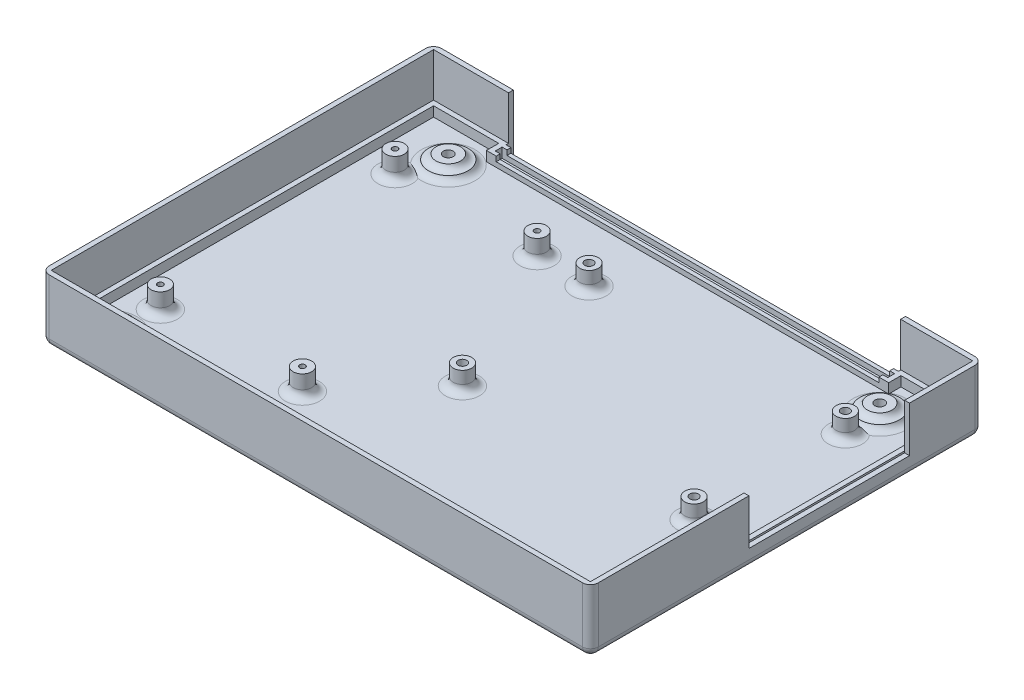
SolidWorks part; units mm, degrees
ref_plane "Front Plane" through (0, 0, 0) normal (0, 0, 1) x (1, 0, 0)
ref_plane "Top Plane" through (0, 0, 0) normal (0, 1, 0) x (1, 0, 0)
ref_plane "Right Plane" through (0, 0, 0) normal (1, 0, 0) x (0, 0, -1)
sketch "Sketch1" plane through (0, 0, 0) normal (0, 1, 0) x (1, 0, 0)
  line L1 (-88.9, -63.5) -> (88.9, -63.5)
  line L2 (-88.9, -63.5) -> (-88.9, 63.5)
  line L3 (-88.9, 63.5) -> (88.9, 63.5)
  line L4 (88.9, -63.5) -> (88.9, 63.5)
  line L5 (-88.9, -63.5) -> (88.9, 63.5) construction
  line L6 (-88.9, 63.5) -> (88.9, -63.5) construction
  point P0 (0, 0)
  dimension "D1" = 177.8
  dimension "D2" = 127
extrude "Boss-Extrude1" add sketch "Sketch1" along normal blind 20.525
sketch "Sketch2" plane through (0, 20.525, 0) normal (0, 1, 0) x (1, 0, 0)
  line L1 (-87.3125, -61.9125) -> (87.3125, -61.9125)
  line L2 (-87.3125, -61.9125) -> (-87.3125, 61.9125)
  line L3 (-87.3125, 61.9125) -> (87.3125, 61.9125)
  line L4 (87.3125, -61.9125) -> (87.3125, 61.9125)
  line L5 (-87.3125, -61.9125) -> (87.3125, 61.9125) construction
  line L6 (-87.3125, 61.9125) -> (87.3125, -61.9125) construction
  point P0 (0, 0)
  dimension "D1" = 174.625
  dimension "D2" = 123.825
extrude "Cut-Extrude1" cut sketch "Sketch2" against normal blind 14.175
fillet "Fillet2" radius 2.54 8 edges at (-88.9, 10.2625, -63.5) (0, 0, -63.5) (88.9, 10.2625, -63.5) (88.9, 0, 0) (88.9, 10.2625, 63.5) (-88.9, 10.2625, 63.5) (-88.9, 0, 0) (0, 0, 63.5)
sketch "Sketch4" plane through (0, 6.35, 0) normal (0, 1, 0) x (1, 0, 0)
  line L0 (87.3125, 61.9125) -> (-87.3125, 61.9125) construction
  line L1 (-63.05, 61.9125) -> (63.95, 61.9125)
  line L2 (-63.05, 61.9125) -> (-63.05, 63.5)
  line L3 (-63.05, 63.5) -> (63.95, 63.5)
  line L4 (63.95, 61.9125) -> (63.95, 63.5)
  line L5 (86.36, 63.5) -> (-86.36, 63.5) construction
  point P8 (0.45, 61.9125)
  dimension "D1" = 63.5
  dimension "D2" = 63.5
  dimension "D3" = 127
extrude "Cut-Extrude2" cut sketch "Sketch4" along normal blind 17.175
sketch "Sketch11" plane through (0, 0, 0) normal (0, 1, 0) x (1, 0, 0)
  line L1 (-85.725, -60.325) -> (85.725, -60.325)
  line L2 (-85.725, -60.325) -> (-85.725, 60.325)
  line L3 (-85.725, 60.325) -> (85.725, 60.325)
  line L4 (85.725, -60.325) -> (85.725, 60.325)
  line L5 (-85.725, -60.325) -> (85.725, 60.325) construction
  line L6 (-85.725, 60.325) -> (85.725, -60.325) construction
  point P0 (0, 0)
  dimension "D1" = 171.45
  dimension "D2" = 120.65
extrude "Cut-Extrude3" cut sketch "Sketch11" along normal blind 3.175 from offset 3.175
sketch "Sketch7" plane through (0, 0, 0) normal (0, 1, 0) x (1, 0, 0)
  line L0 (-87.3125, -61.9125) -> (87.3125, -61.9125) construction
  line L1 (-51.6011, -60.325) -> (-33.4411, -60.325)
  line L2 (-51.6011, -60.325) -> (-51.6011, -58.1104)
  line L3 (-51.6011, -58.1104) -> (-33.4411, -58.1104)
  line L4 (-33.4411, -60.325) -> (-33.4411, -58.1104)
  point P4 (-42.5211, -60.325)
  dimension "D1" = 1.5875
extrude "Boss-Extrude3" add sketch "Sketch7" along normal blind 9.525
mirror "Mirror1" about plane through (0, 0, 0) normal (1, 0, 0) of "Boss-Extrude3"
sketch "Sketch16" plane through (0, 3.175, 0) normal (0, 1, 0) x (1, 0, 0)
  circle A0 centre (-77.7553, -52.3501) radius 3.9687
extrude "Cut-Extrude5" cut sketch "Sketch16" along normal blind 2.54 from surface at -3.175 contours A0 starting at face at (0, 0, 0)
sketch "Sketch17" plane through (0, 0, 0) normal (0, 1, 0) x (1, 0, 0)
  line L1 (-63.05, 63.5) -> (63.95, 63.5)
  line L2 (-63.05, 63.5) -> (-63.05, 61.9125)
  line L3 (-63.05, 61.9125) -> (63.95, 61.9125)
  line L4 (63.95, 63.5) -> (63.95, 61.9125)
extrude "Cut-Extrude6" cut sketch "Sketch17" along normal blind 12.7
sketch "Sketch18" plane through (0, 0, 0) normal (0, 1, 0) x (1, 0, 0)
  line L0 (85.725, 60.325) -> (-85.725, 60.325) construction
  line L1 (-63.05, 61.9125) -> (64.0466, 61.9125)
  line L2 (-63.05, 61.9125) -> (-63.05, 60.325)
  line L3 (-63.05, 60.325) -> (64.0466, 60.325)
  line L4 (64.0466, 61.9125) -> (64.0466, 60.325)
extrude "Cut-Extrude7" cut sketch "Sketch18" along normal blind 3.175 from surface at 3.175 starting at face at (0, 3.175, 39.4785)
sketch "Sketch20" plane through (0, 3.175, 0) normal (0, 1, 0) x (1, 0, 0)
  line L0 (-63.05, 61.9125) -> (-63.05, 60.325) construction
  line L1 (-64.6375, 61.1187) -> (65.6341, 61.1187)
  line L2 (-64.6375, 61.1187) -> (-64.6375, 56.3562)
  line L3 (-64.6375, 56.3562) -> (65.6341, 56.3562)
  line L4 (65.6341, 61.1187) -> (65.6341, 56.3562)
  line L5 (64.0466, 60.325) -> (64.0466, 61.9125) construction
  line L6 (-63.05, 61.9125) -> (-87.3125, 61.9125) construction
  dimension "D1" = 1.5875
  dimension "D2" = 1.5875
  dimension "D3" = 4.7625
  dimension "D4" = 0.7937
extrude "Boss-Extrude7" add sketch "Sketch20" along normal blind 3.175
sketch "Sketch21" plane through (0, 3.175, 0) normal (0, 1, 0) x (1, 0, 0)
  line L1 (-63.05, 61.9125) -> (64.0466, 61.9125)
  line L2 (-63.05, 61.9125) -> (-63.05, 61.1187)
  line L3 (-63.05, 61.1187) -> (64.0466, 61.1187)
  line L4 (64.0466, 61.9125) -> (64.0466, 61.1187)
extrude "Cut-Extrude10" cut sketch "Sketch21" against normal blind 3.175
sketch "Sketch23" plane through (0, 6.35, 0) normal (0, 1, 0) x (1, 0, 0)
  line L0 (65.6341, 56.3562) -> (65.6341, 60.325) construction
  line L1 (-63.05, 59.8487) -> (64.0466, 59.8487)
  line L2 (-63.05, 59.8487) -> (-63.05, 57.6262)
  line L3 (-63.05, 57.6262) -> (64.0466, 57.6262)
  line L4 (64.0466, 59.8487) -> (64.0466, 57.6262)
  line L5 (-64.6375, 56.3562) -> (65.6341, 56.3562) construction
  line L6 (64.0466, 61.1187) -> (-63.05, 61.1187) construction
  line L7 (-64.6375, 60.325) -> (-64.6375, 56.3562) construction
  dimension "D1" = 1.5875
  dimension "D2" = 1.27
  dimension "D3" = 1.27
  dimension "D4" = 1.5875
extrude "Cut-Extrude11" cut sketch "Sketch23" against normal blind 3.175
sketch "Sketch24" plane through (0, 6.35, 0) normal (0, 1, 0) x (1, 0, 0)
  line L0 (64.0466, 61.1187) -> (-63.05, 61.1187) construction
  line L1 (-61.4625, 61.1187) -> (62.4591, 61.1187)
  line L2 (-61.4625, 61.1187) -> (-61.4625, 56.3562)
  line L3 (-61.4625, 56.3562) -> (62.4591, 56.3562)
  line L4 (62.4591, 61.1187) -> (62.4591, 56.3562)
  line L5 (-64.6375, 56.3562) -> (65.6341, 56.3562) construction
  line L6 (-63.05, 59.8487) -> (-63.05, 57.6262) construction
  line L8 (64.0466, 57.6262) -> (64.0466, 59.8487) construction
  dimension "D1" = 1.5875
  dimension "D2" = 1.5875
extrude "Cut-Extrude13" cut sketch "Sketch24" against normal blind 1.5875
sketch "Sketch26" plane through (0, 3.175, 0) normal (0, 1, 0) x (1, 0, 0)
  line L0 (88.9, -60.96) -> (88.9, 60.96) construction
  line L3 (86.36, 63.5) -> (63.95, 63.5) construction
  circle A0 centre (69.85, 49.2125) radius 6.35
  dimension "D1" = 12.7
  dimension "D2" = 19.05
  dimension "D3" = 14.2875
extrude "Boss-Extrude8" add sketch "Sketch26" along normal blind 1.5875
sketch "Sketch28" plane through (0, 4.7625, 0) normal (0, 1, 0) x (1, 0, 0)
  circle A0 centre (69.85, 49.2125) radius 3.9688
extrude "Boss-Extrude9" add sketch "Sketch28" along normal blind 1.5875
sketch "Sketch29" plane through (0, 6.35, 0) normal (0, 1, 0) x (1, 0, 0)
  circle A0 centre (69.85, 49.2125) radius 1.5875
extrude "Cut-Extrude14" cut sketch "Sketch29" against normal blind 12.7
sketch "Sketch30" plane through (0, 6.35, 0) normal (0, 1, 0) x (1, 0, 0)
  circle A0 centre (69.85, 49.2125) radius 3.9688
extrude "Cut-Extrude15" cut sketch "Sketch30" along normal blind 2.54 from surface at -6.35 starting at face at (69.85, 0, -50.8)
mirror "Mirror7" about plane through (0, 0, 0) normal (1, 0, 0) of "Cut-Extrude15", "Cut-Extrude14", "Boss-Extrude9", "Boss-Extrude8"
sketch "Sketch31" plane through (0, 3.175, 0) normal (0, 1, 0) x (1, 0, 0)
  line L0 (86.36, 63.5) -> (63.95, 63.5) construction
  line L1 (88.9, -60.96) -> (88.9, 60.96) construction
  circle A0 centre (69.85, 38.1) radius 3
  circle A1 centre (69.85, 38.1) radius 1.4
  circle A2 centre (-13.15, 38.1) radius 3
  circle A3 centre (-13.15, 38.1) radius 1.4
  circle A4 centre (69.35, -10.3974) radius 3
  circle A5 centre (69.35, -10.3974) radius 1.4
  circle A6 centre (-5.65, -10.4) radius 1.4
  circle A7 centre (-5.65, -10.4) radius 3
  dimension "D1" = 25.4
  dimension "D2" = 83
  dimension "D5" = 75
  dimension "D3" = 19.05
  dimension "D4" = 48.5
  dimension "D6" = 48.5
extrude "Boss-Extrude10" add sketch "Sketch31" along normal blind 6.5
sketch "Sketch32" plane through (0, 3.175, 0) normal (0, 1, 0) x (1, 0, 0)
  circle A0 centre (-76.0528, 38.1791) radius 3
  circle A1 centre (-30.0528, 38.1779) radius 3
  circle A2 centre (-76.0528, -37.8209) radius 3
  circle A3 centre (-30.0528, -37.8221) radius 3
  circle A5 centre (-76.0528, 38.1791) radius 0.9
  circle A6 centre (-30.0528, 38.1779) radius 0.9
  circle A8 centre (-30.0528, -37.8221) radius 0.9
  circle A9 centre (-76.0528, -37.8209) radius 0.9
  dimension "D2" = 46
  dimension "D4" = 76
  dimension "D1" = 76
  dimension "D3" = 46
extrude "Boss-Extrude11" add sketch "Sketch32" along normal blind 7
sketch "Sketch33" plane through (0, 3.175, 0) normal (0, 1, 0) x (1, 0, 0)
  line L0 (-86.36, -63.5) -> (86.36, -63.5) construction
  line L1 (-88.9, 60.96) -> (-88.9, -60.96) construction
  line L2 (88.9, -60.96) -> (88.9, 60.96) construction
  circle A0 centre (-77.7875, -52.3875) radius 6.35
  circle A1 centre (77.7875, -52.3875) radius 6.35
  dimension "D1" = 12.7
  dimension "D4" = 12.7
  dimension "D2" = 11.1125
  dimension "D3" = 11.1125
  dimension "D5" = 11.1125
  dimension "D6" = 11.1125
extrude "Boss-Extrude13" add sketch "Sketch33" along normal blind 1.5875
sketch "Sketch34" plane through (0, 4.7625, 0) normal (0, 1, 0) x (1, 0, 0)
  circle A0 centre (-77.7875, -52.3875) radius 3.9687
  circle A1 centre (77.7875, -52.3875) radius 3.9687
extrude "Boss-Extrude14" add sketch "Sketch34" along normal blind 1.5875
sketch "Sketch35" plane through (0, 6.35, 0) normal (0, 1, 0) x (1, 0, 0)
  circle A0 centre (-77.7875, -52.3875) radius 1.5875
  circle A1 centre (77.7875, -52.3875) radius 1.5875
extrude "Cut-Extrude16" cut sketch "Sketch35" against normal blind 12.7
mirror "Mirror8" about plane through (0, 0, 0) normal (1, 0, 0) of "Cut-Extrude5"
fillet "Fillet3" radius 2.54 16 edges at (-77.7875, 4.7625, 56.3562) (-69.85, 4.7625, -45.2437) (77.7875, 4.7625, 56.3562) (77.7875, 3.175, 46.0375) (69.85, 4.7625, -45.2437) (69.85, 3.175, -55.5625) (69.35, 3.175, 7.3974) (69.85, 3.175, -41.1) (-13.15, 3.175, -41.1) (-5.65, 3.175, 7.4) (-30.0528, 3.175, 34.8221) (-30.0528, 3.175, -41.1779) (-76.0528, 3.175, 34.8209) (-77.7875, 3.175, 46.0375) (-69.85, 3.175, -42.8625) (-76.0528, 3.175, -41.1791)
sketch "Sketch36" plane through (0, 20.525, 0) normal (0, 1, 0) x (1, 0, 0)
  line L0 (87.3125, -61.9125) -> (87.3125, 61.9125) construction
  line L1 (87.3125, 39.8297) -> (88.9, 39.8297)
  line L2 (87.3125, 39.8297) -> (87.3125, -12.1729)
  line L3 (87.3125, -12.1729) -> (88.9, -12.1729)
  line L4 (88.9, 39.8297) -> (88.9, -12.1729)
  line L5 (88.9, -60.96) -> (88.9, 60.96) construction
extrude "Cut-Extrude17" cut sketch "Sketch36" against normal blind 14.75
equation "\"0.125n\"=0.25"
